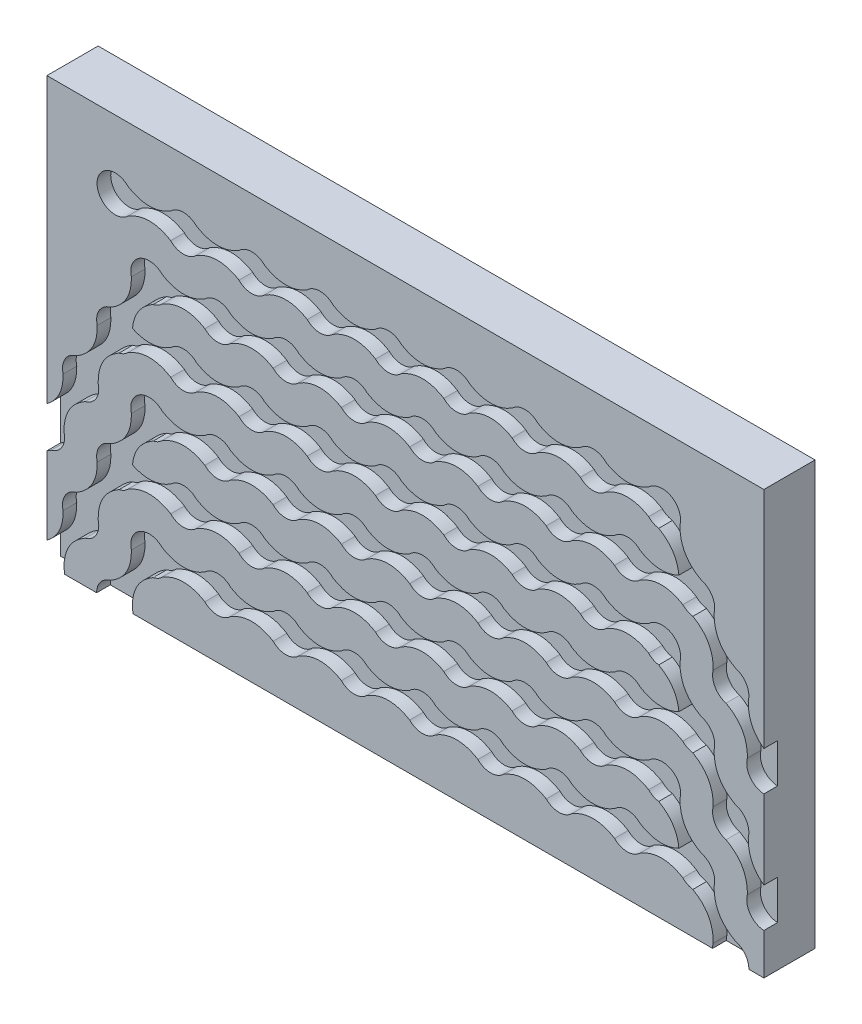
SolidWorks part; units mm, degrees
ref_plane "Front Plane" through (0, 0, 0) normal (0, 0, 1) x (1, 0, 0)
ref_plane "Top Plane" through (0, 0, 0) normal (0, 1, 0) x (1, 0, 0)
ref_plane "Right Plane" through (0, 0, 0) normal (1, 0, 0) x (0, 0, -1)
sketch "Sketch2" plane through (0, 0, 0) normal (0, 0, 1) x (1, 0, 0)
  line L1 (-31.0609, 47.3202) -> (102.2891, 47.3202)
  line L2 (-31.0609, 47.3202) -> (-31.0609, -31.371)
  line L3 (-31.0609, -31.371) -> (102.2891, -31.371)
  line L4 (102.2891, 47.3202) -> (102.2891, -31.371)
  dimension "D1" = 133.35
  dimension "D2" = 78.6911
extrude "Boss-Extrude1" add sketch "Sketch2" along normal blind 9.525
sketch "Sketch1" plane through (0, 0, 9.525) normal (0, 0, 1) x (1, 0, 0)
  line L0 (-23.8319, 34.6202) -> (-5.6609, 34.6202) construction
  line L1 (-18.3609, 34.6202) -> (-18.3609, 37.9936) construction
  line L2 (-12.0109, 28.2702) -> (-12.0109, 40.9702) construction
  line L3 (-18.3609, 34.6202) -> (-12.0109, 40.9702) construction
  line L4 (-12.0109, 40.9702) -> (-5.6609, 34.6202) construction
  line L5 (-18.3609, 35.8108) -> (-12.0109, 35.8108) construction
  line L6 (102.2891, 47.3202) -> (-31.0609, 47.3202) construction
  line L9 (-31.0609, 47.3202) -> (-31.0609, -31.371) construction
  arc A0 (-15.9755, 37.0056) -> (-15.9755, 32.2348) centre (-18.3609, 34.6202) ccw
  arc A1 (-8.0463, 32.2348) -> (-8.0463, 37.0056) centre (-5.6609, 34.6202) ccw
  spline S0 degree 2 poles (-15.9755, 37.0056) (-12.0109, 34.616) (-8.0463, 37.0056) knots 0 0 0 1 1 1
  spline S1 degree 2 poles (-15.9755, 32.2348) (-12.0109, 34.6243) (-8.0463, 32.2348) knots 0 0 0 1 1 1
  point P6 (-15.9755, 37.0056)
  point P7 (-12.0109, 34.6202)
  point P10 (-8.0463, 37.0056)
  dimension "D1" = 6.7469
  dimension "D2" = 6.7469
  dimension "D3" = 12.7
  dimension "D4" = 1.1906
  dimension "D5" = 12.7
  dimension "D6" = 12.7
extrude "Cut-Extrude1" cut sketch "Sketch1" against normal blind 2.54
pattern_linear "LPattern1" count 8 spacing 12.7 along (1, 0, 0) of "Cut-Extrude1"
sketch "Sketch3" plane through (0, 0, 6.985) normal (0, 0, 1) x (1, 0, 0)
  line L0 (113.141, 113.41) -> (138.864, 68.8563) construction
pattern_linear "LPattern3" count 2 spacing 12.7 along (0.5, -0.866, 0) of "LPattern1"
pattern_linear "LPattern4" count 3 spacing 21.997 along (0, -1, 0) of "LPattern3", "LPattern1", "Cut-Extrude1"
sketch "Sketch6" plane through (0, 0, 9.525) normal (0, 0, 1) x (1, 0, 0)
  line L0 (81.7399, 37.5659) -> (89.7766, 23.6459) construction
  line L1 (83.4266, 34.6444) -> (86.3481, 36.3312) construction
  line L2 (81.1024, 25.9702) -> (92.1009, 32.3202) construction
  line L3 (83.4266, 34.6444) -> (92.1009, 32.3202) construction
  line L4 (92.1009, 32.3202) -> (89.7766, 23.6459) construction
  line L5 (84.4577, 35.2398) -> (87.6327, 29.7405) construction
  arc A0 (86.6851, 33.7713) -> (82.5535, 31.386) centre (83.4266, 34.6444) ccw
  arc A1 (86.5181, 24.519) -> (90.6497, 26.9044) centre (89.7766, 23.6459) ccw
  spline S0 degree 2 poles (86.6851, 33.7713) (86.5981, 29.1431) (90.6497, 26.9044) knots 0 0 0 1 1 1
  spline S1 degree 2 poles (82.5535, 31.386) (86.6052, 29.1472) (86.5181, 24.519) knots 0 0 0 1 1 1
  point P5 (86.6851, 33.7713)
  point P6 (86.6016, 29.1452)
  point P9 (90.6497, 26.9044)
  dimension "D1" = 6.7469
  dimension "D2" = 6.7469
  dimension "D3" = 12.7
  dimension "D4" = 1.1906
extrude "Cut-Extrude2" cut sketch "Sketch6" against normal blind 2.54
pattern_linear "LPattern5" count 3 spacing 12.7 along (0.5, -0.866, 0) of "Cut-Extrude2"
pattern_linear "LPattern6" count 3 spacing 21.997 along (0, -1, 0) of "LPattern5"
sketch "Sketch7" plane through (0, 0, 9.525) normal (0, 0, 1) x (1, 0, 0)
  line L0 (-21.1778, 7.8871) -> (-12.0923, 23.6237) construction
  line L1 (-18.4423, 12.6252) -> (-21.3638, 14.3119) construction
  line L2 (-9.768, 14.9494) -> (-20.7665, 21.2994) construction
  line L3 (-18.4423, 12.6252) -> (-20.7665, 21.2994) construction
  line L4 (-20.7665, 21.2994) -> (-12.0923, 23.6237) construction
  line L5 (-19.4734, 13.2205) -> (-16.2984, 18.7197) construction
  arc A0 (-19.3154, 15.8837) -> (-15.1838, 13.4983) centre (-18.4423, 12.6252) ccw
  arc A1 (-11.2192, 20.3652) -> (-15.3508, 22.7506) centre (-12.0923, 23.6237) ccw
  spline S0 degree 2 poles (-19.3154, 15.8837) (-15.2637, 18.1224) (-15.3508, 22.7506) knots 0 0 0 1 1 1
  spline S1 degree 2 poles (-15.1838, 13.4983) (-15.2709, 18.1265) (-11.2192, 20.3652) knots 0 0 0 1 1 1
  point P5 (-19.3154, 15.8837)
  point P6 (-15.2673, 18.1244)
  point P9 (-15.3508, 22.7506)
  dimension "D1" = 6.7469
  dimension "D2" = 6.7469
  dimension "D3" = 12.7
  dimension "D4" = 1.1906
extrude "Cut-Extrude3" cut sketch "Sketch7" against normal blind 2.54
sketch "Sketch8" plane through (0, 0, 9.525) normal (0, 0, 1) x (1, 0, 0)
  line L0 (-130.9367, -65.4959) -> (-114.4625, -36.9619) construction
pattern_linear "LPattern7" count 4 spacing 12.7 along (-0.5, -0.866, 0) of "Cut-Extrude3"
pattern_linear "LPattern8" count 3 spacing 21.997 along (0, -1, 0) of "LPattern7"
scale "Scale1" scale about centroid uniform scaling yes scale factor 0.75
equation "\"large_diameter\" = 1/4in"
equation "\"small_diameter\" = 1/8in"
equation "\"arc_height\" = 1/32in"
equation "\"chain_space\" = 1/2in"
equation "\"chain_thickness\" = 1/16in"
equation "\"outer_height\" = 3/16in"
equation "\"inner_height\" = 2/16in"
equation "\"give\" = 1/16in"
equation "\"board_base\" = 10"
equation "\"board_rows\" = 3"
equation "\"D2@Sketch1\"= \"large_diameter\" + \"give\""
equation "\"D3@Sketch1\"= \"chain_space\""
equation "\"D4@Sketch1\"= \"arc_height\" + \"give\""
equation "\"D1@Sketch2\"=\"chain_space\"*(\"board_base\"+.5)"
equation "\"D3@LPattern1\"=\"chain_space\""
equation "\"D1@LPattern1\"=\"board_base\"-2"
equation "\"D3@LPattern3\"=\"chain_space\""
equation "\"D3@LPattern4\"=\"chain_space\"*sin(60)*2"
equation "\"D2@Sketch2\"=\"board_rows\"*\"chain_space\"*2*sin(60)+.5"
equation "\"D3@LPattern6\"=\"chain_space\"*sin(60)*2"
equation "\"D3@LPattern7\"=\"chain_space\""
equation "\"D3@LPattern8\"=\"chain_space\"*2*sin(60)"
